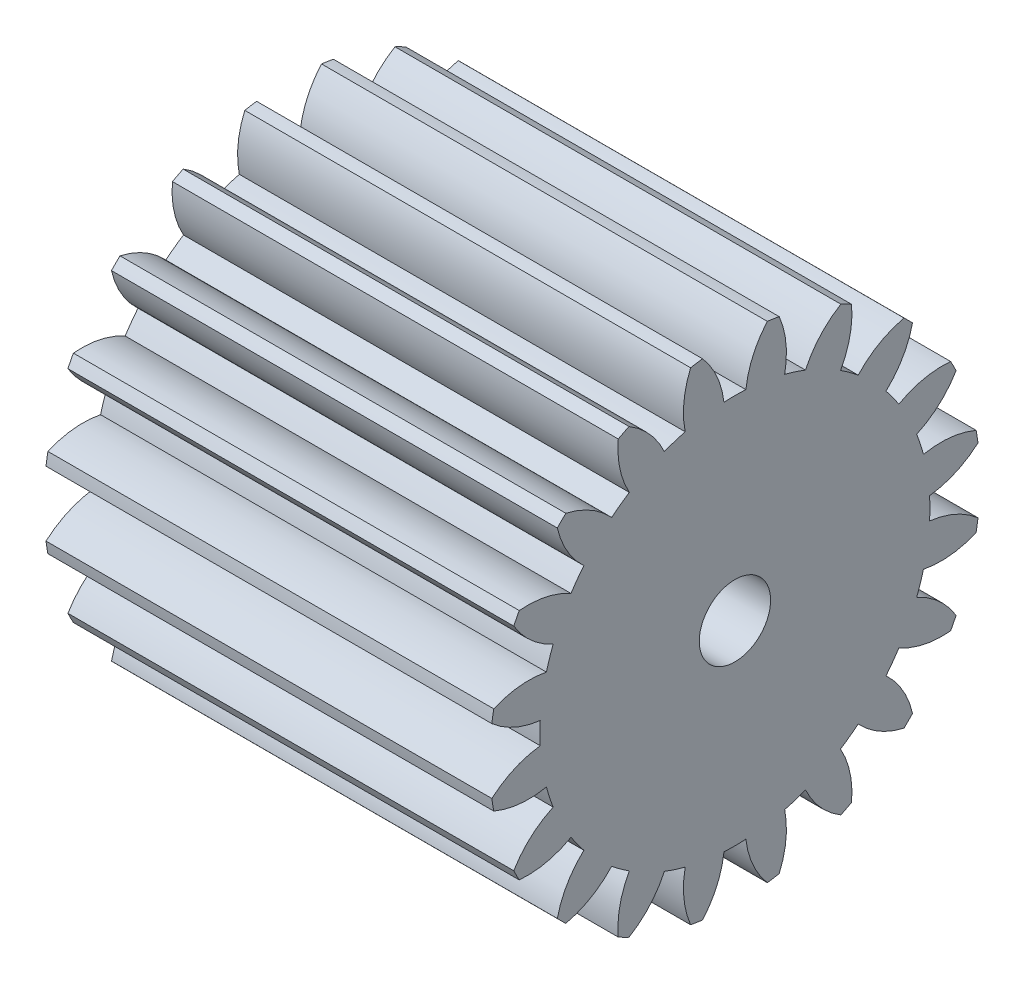
SolidWorks part; units mm, degrees
ref_plane "Plane1" through (0, 0, 0) normal (0, 0, 1) x (1, 0, 0)
ref_plane "Plane2" through (0, 0, 0) normal (0, 1, 0) x (1, 0, 0)
ref_plane "EDGE" through (0, 0, 0) normal (1, 0, 0) x (0, 0, -1)
sketch "HoldingSke" plane through (0, 0, 0) normal (0, 1, 0) x (1, 0, 0)
  line L0 (0, 0) -> (3.7588, -1.3681)
  line L1 (-15, 0) -> (100, 0) construction
  line L2 (0, 0) -> (-2.1039, 2.3779)
  line L3 (0, 0) -> (-11.863, 4.5341)
  line L4 (0, 0) -> (8.1152, 2.9537)
  line L5 (0, 0) -> (-46.8476, -17.4728)
  line L6 (0, 0) -> (-4.1448, -2.7965)
  line L7 (-2.1039, 2.3779) -> (8.6586, 51.2059)
  line L8 (-76.2, 54.61) -> (-76.1, 54.61)
  line L9 (-71.009, 38.7566) -> (-53.1078, 45.2721)
  line L10 (-76.2, 71.12) -> (104.1128, 71.12)
  line L11 (0, 0) -> (-5, 0)
  line L12 (-76.2, 101.6) -> (-76.192, 101.6)
  line L13 (24.9733, 27.94) -> (52.9518, 28.4284)
  line L14 (24.9733, 27.94) -> (24.9743, 27.94)
  line L15 (24.9733, 27.94) -> (100.4006, 29.5858)
  line L16 (-63.627, -0.25) -> (-12.827, -0.25)
  circle A0 centre (0, 0) radius 0.4
  circle A1 centre (0, 0) radius 2.1865
  circle A2 centre (0, 0) radius 37.5
  circle A3 centre (0, 0) radius 0.4
  dimension "Num_teeth" = 20
  dimension "Pitch_radius" = 180.3128
  dimension "Width" = 5
  dimension "Thickness" = 5
sketch "BasProSke" plane through (0, 0, 0) normal (0, 1, 0) x (1, 0, 0)
  line L0 (-10, 0) -> (60, 0) construction
  line L1 (0, 0) -> (0, 2.75)
  line L2 (0, 0) -> (5, 0)
  line L3 (5, 0) -> (5, 2.75)
  line L4 (5, 2.75) -> (0, 2.75)
  dimension "Thickness" = 5
  dimension "Diameter" = 5.5
revolve "Base-Revolve" add sketch "BasProSke" angle 360 about L0
sketch "TooCutSke" plane through (0, 0, 0) normal (1, 0, 0) x (0, 0, -1)
  line L1 (0, 0) -> (0, 107) construction
  line L2 (0, 0) -> (-0.2101, 2.4912) construction
  line L3 (0, 0) -> (-0.7801, 4.9253) construction
  line L4 (-0.2101, 2.4912) -> (-0.39, 2.4627) construction
  arc A0 (0.1226, 2.1831) -> (-0.1226, 2.1831) centre (0, 0) ccw
  arc A1 (0.384, 2.7487) -> (-0.384, 2.7487) centre (0, 0) ccw
  circle A2 centre (0, 0) radius 2.5 construction
  circle A3 centre (0, 0) radius 2.3492 construction
  arc A4 (-0.1226, 2.1831) -> (-0.384, 2.7487) centre (-1.1159, 2.0673) ccw
  arc A5 (0.384, 2.7487) -> (0.1226, 2.1831) centre (1.1159, 2.0673) ccw
extrude "ToothCut" cut sketch "TooCutSke" along normal through all
fillet "Breaks" [suppressed] radius 0.005 tangent propagation no
fillet "RootFillets" [suppressed] radius 0.0635
pattern_circular "TeethCuts" count 20 every 18 about axis through (-10, 0, 0) along (1, 0, 0) of "ToothCut", "RootFillets", "Breaks"
sketch "HubNeaOneSke" plane through (0, 0, 0) normal (-1, 0, 0) x (0, 0, 1)
  circle A0 centre (0, 0) radius 2.1865
  dimension "Diameter" = 4.373
extrude "HubNearOne" [suppressed] add sketch "HubNeaOneSke" along normal blind 45.0001
sketch "HubNeaBotSke" plane through (0, 0, 0) normal (-1, 0, 0) x (0, 0, 1)
  circle A0 centre (0, 0) radius 2.1865
  dimension "Diameter" = 4.373
extrude "HubNearBoth" [suppressed] add sketch "HubNeaBotSke" along normal blind 22.5
ref_plane "FarPln" through (5, 0, 0) normal (1, 0, 0) x (0, 0, -1)
sketch "HubFarSke" plane through (5, 0, 0) normal (1, 0, 0) x (0, 0, -1)
  circle A0 centre (0, 0) radius 2.1865
  dimension "Diameter" = 4.373
extrude "HubFar" [suppressed] add sketch "HubFarSke" along normal blind 22.5
sketch "BorSke" plane through (0, 0, 0) normal (1, 0, 0) x (0, 0, -1)
  circle A0 centre (0, 0) radius 0.4
  dimension "Diameter" = 0.8
extrude "Bore" cut sketch "BorSke" along normal mid plane 100.0001
sketch "KeySke" plane through (0, 0, 0) normal (1, 0, 0) x (0, 0, -1)
  line L0 (-0.05, 0) -> (-0.05, 0.5)
  line L1 (-0.05, 0.5) -> (0.05, 0.5)
  line L2 (0.05, 0.5) -> (0.05, 0)
  line L3 (0, 0) -> (0, 34) construction
  line L4 (-0.05, 0) -> (0.05, 0)
  dimension "Width" = 0.1
extrude "Keyway" [suppressed] cut sketch "KeySke" along normal mid plane 100.0001
pattern_circular "Keyway2" [suppressed] count 2 every 90 about axis through (-10, 0, 0) along (1, 0, 0)
ref_axis "Central Axis" through (5, 0, 0) along (-1, 0, 0)
ref_plane "Front Edge" through (5, 0, 0) normal (1, 0, 0) x (0, 0, -1)
equation "' \"Module@HoldingSke\" = 6.35"
equation "' \"Num_teeth@HoldingSke\" = 12"
equation "' \"Ap@HoldingSke\" =  20"
equation "' \"Ap@HoldingSke\" = 20"
equation "' \"Width@HoldingSke\" = 0.5 * 25.4"
equation "' \"Hub_dia@HoldingSke\"= 1 * 25.4"
equation "' \"Hub_dia@HoldingSke\" = 1 * 25.4"
equation "' \"Overall_len@HoldingSke\" = 1.0 * 25.4"
equation "' \"Bore@HoldingSke\" = 0.75 * 25.4"
equation "' \"T_dim@HoldingSke\" = 0.1 * 25.4"
equation "' \"Width@KeySke\" = 0.25 * 25.4"
equation "' \"Show_teeth@HoldingSke\" = 13"
equation "' \"Backlash@HoldingSke\" = 0.009 * 25.4"
equation "' \"Addendum_fac@HoldingSke\" = 1.0"
equation "' \"Dedendum_fac@HoldingSke\" = 1.25"
equation "' \"Dedendum_add@HoldingSke\" = 0.00005 * 25.4"
equation "' \"Clearance_fac@HoldingSke\" = 0.25"
equation "\"Pitch@HoldingSke\" = 1 / \"Module@HoldingSke\""
equation "\"Overcut_dia@TooCutSke\" = (\"Num_teeth@HoldingSke\" + 2 * \"Addendum_fac@HoldingSke\") / \"Pitch@HoldingSke\" + 0.002 * 25.4"
equation "\"Pitch_dia@TooCutSke\" = \"Num_teeth@HoldingSke\" / \"Pitch@HoldingSke\""
equation "\"Base_dia@TooCutSke\" = \"Num_teeth@HoldingSke\" / \"Pitch@HoldingSke\" * cos((\"Ap@HoldingSke\"  * 3.14159265 / 180))"
equation "\"Root_dia@TooCutSke\" = (\"Num_teeth@HoldingSke\" + 2) / \"Pitch@HoldingSke\" - 2 * (\"Addendum_fac@HoldingSke\" + \"Dedendum_fac@HoldingSke\") / \"Pitch@HoldingSke\" - \"Dedendum_add@HoldingSke\" * 2"
equation "\"Half_ang@TooCutSke\" = 180 / \"Num_teeth@HoldingSke\""
equation "\"Half_CT@TooCutSke\" = \"Num_teeth@HoldingSke\" / \"Pitch@HoldingSke\" * sin((3.14159265 / 2 / \"Num_teeth@HoldingSke\")) / 2 - 7 * \"Backlash@HoldingSke\" / 4"
equation "\"Flank_rad@TooCutSke\" = \"Num_teeth@HoldingSke\" / \"Pitch@HoldingSke\" / 5"
equation "\"Radius@RootFillets\" = \"Clearance_fac@HoldingSke\" / \"Pitch@HoldingSke\" + \"Dedendum_add@HoldingSke\""
equation "\"Break_rad@Breaks\" = 0.02 / \"Pitch@HoldingSke\""
equation "\"Thickness@HoldingSke\" = \"Width@HoldingSke\""
equation "\"OAL@HoldingSke\" = \"Thickness@HoldingSke\""
equation "\"MHD@HoldingSke\" = (\"Num_teeth@HoldingSke\" + 2) / \"Pitch@HoldingSke\" - 2 * (\"Addendum_fac@HoldingSke\" + \"Dedendum_fac@HoldingSke\")  / \"Pitch@HoldingSke\" - \"Dedendum_add@HoldingSke\" * 2"
equation "\"MBD@HoldingSke\" = (\"Num_teeth@HoldingSke\" + 2) / \"Pitch@HoldingSke\" - 2 * (\"Addendum_fac@HoldingSke\" + \"Dedendum_fac@HoldingSke\")  / \"Pitch@HoldingSke\" - \"Dedendum_add@HoldingSke\" * 2 - 0.002 * 25.4"
equation "\"MHD@HoldingSke\" = ((sgn( \"MHD@HoldingSke\" - \"Hub_dia@HoldingSke\" )-1)*( \"MHD@HoldingSke\" - \"Hub_dia@HoldingSke\" ))/-2+ \"Hub_dia@HoldingSke\""
equation "\"MBD@HoldingSke\" = ((sgn( \"MBD@HoldingSke\" - \"Bore@HoldingSke\" )-1)*( \"MBD@HoldingSke\" - \"Bore@HoldingSke\" ))/-2+ \"Bore@HoldingSke\""
equation "\"OAL@HoldingSke\" = ((sgn( \"OAL@HoldingSke\" - \"Overall_len@HoldingSke\" )+1)*( \"OAL@HoldingSke\" - \"Overall_len@HoldingSke\" ))/2 + \"Overall_len@HoldingSke\" + 0.000002 * 25.4"
equation "\"Num_teeth@TeethCuts\" = int( \"Show_teeth@HoldingSke\" ) + 1"
equation "\"Num_teeth@TeethCuts\" = ((sgn( \"Num_teeth@TeethCuts\" - \"Num_teeth@HoldingSke\" )-1)*( \"Num_teeth@TeethCuts\" - \"Num_teeth@HoldingSke\" ))/-2+ \"Num_teeth@HoldingSke\""
equation "\"Num_teeth@TeethCuts\" = ((sgn( \"Num_teeth@TeethCuts\" - 2.0)+1)*( \"Num_teeth@TeethCuts\" - 2.0))/2 +2.0"
equation "\"Angle@TeethCuts\" = 360.0 / \"Num_teeth@HoldingSke\""
equation "\"Diameter@BasProSke\" = (\"Num_teeth@HoldingSke\" + 2 * \"Addendum_fac@HoldingSke\") / \"Pitch@HoldingSke\""
equation "\"Thickness@BasProSke\"  = \"Thickness@HoldingSke\""
equation "' \"Fillet_rad@BasProSke\" =  \"Thickness@HoldingSke\" * 0.05"
equation "' \"Fillet_rad@BasProSke\" = \"Thickness@HoldingSke\" * 0.05"
equation "\"MHD@HoldingSke\" = ((sgn( \"MHD@HoldingSke\" - \"Root_dia@TooCutSke\" )-1)*( \"MHD@HoldingSke\" - \"Root_dia@TooCutSke\" ))/-2+ \"Root_dia@TooCutSke\""
equation "\"Diameter@HubNeaOneSke\" = \"MHD@HoldingSke\""
equation "\"Length@HubNearOne\" = \"OAL@HoldingSke\" - \"Thickness@BasProSke\""
equation "\"Diameter@HubNeaBotSke\" = \"MHD@HoldingSke\""
equation "\"Length@HubNearBoth\" = ( \"OAL@HoldingSke\" - \"Thickness@BasProSke\" ) / 2.0"
equation "\"Thickness@FarPln\" = \"Thickness@BasProSke\""
equation "\"Diameter@HubFarSke\" = \"MHD@HoldingSke\""
equation "\"Length@HubFar\" = ( \"OAL@HoldingSke\" - \"Thickness@BasProSke\" ) / 2.0"
equation "\"Diameter@BorSke\" = \"MBD@HoldingSke\""
equation "\"D1@Bore\" = \"OAL@HoldingSke\" * 2.0"
equation "\"D1@Keyway\" = \"OAL@HoldingSke\" * 2.0"
equation "\"Offset@KeySke\" = \"T_dim@HoldingSke\" + \"MBD@HoldingSke\" / 2.0"
